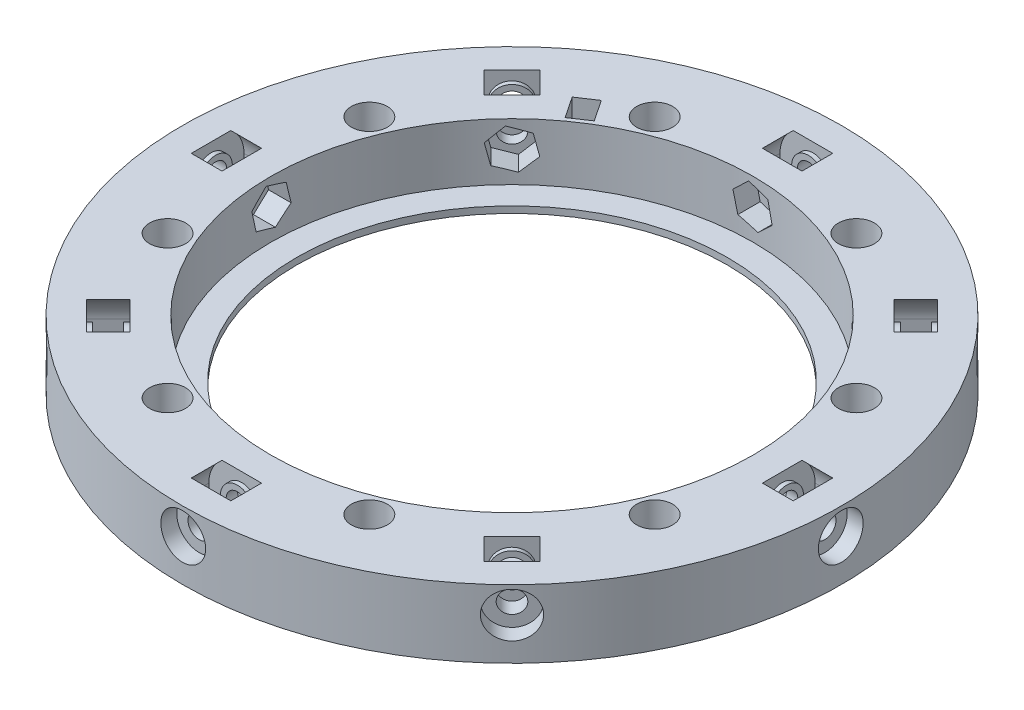
SolidWorks part; units mm, degrees
ref_plane "Front Plane" through (0, 0, 0) normal (0, 0, 1) x (1, 0, 0)
ref_plane "Top Plane" through (0, 0, 0) normal (0, 1, 0) x (1, 0, 0)
ref_plane "Right Plane" through (0, 0, 0) normal (1, 0, 0) x (0, 0, -1)
sketch "Sketch1" plane through (0, 0, 0) normal (0, 1, 0) x (1, 0, 0)
  circle A0 centre (0, 0) radius 75
  dimension "D1" = 150
extrude "Extrude-Thin1" add sketch "Sketch1" along normal blind 15.5 thin thin type one direction reverse wall 20.075
ref_plane "Plane1" through (0, 0, 75) normal (0, 0, 1) x (1, 0, 0)
sketch "Sketch2" plane through (0, 0, 75) normal (0, 0, 1) x (1, 0, 0)
  line L0 (-75, 0) -> (75, 0) construction
  line L1 (-7.5, 9.5) -> (-7.5, 0)
  line L2 (-7.5, 0) -> (7.5, 0)
  line L3 (7.5, 0) -> (7.5, 9.5)
  line L4 (75, 15.5) -> (-75, 15.5) construction
  arc A0 (7.5, 9.5) -> (-7.5, 9.5) centre (0, 9.5) ccw
  dimension "D1" = 15
  dimension "D2" = 6
extrude "Cut-Extrude1" cut sketch "Sketch2" against normal blind 7 from offset 6.5 offset against normal yes
sketch "Sketch3" plane through (0, 15.5, 0) normal (0, 1, 0) x (1, 0, 0)
  line L0 (0, 0) -> (0, 50000) construction
  line L1 (0, 0) -> (-19134.1716, 46193.9766) construction
  circle A0 centre (-22.961, 55.4328) radius 4.1
  dimension "D2" = 8.2
  dimension "D1" = 22.5
  dimension "D3" = 60
extrude "Cut-Extrude2" cut sketch "Sketch3" against normal blind 7.1
sketch "Sketch4" plane through (0, 15.5, 0) normal (0, 1, 0) x (1, 0, 0)
  circle A0 centre (-22.961, 55.4328) radius 2.05
  dimension "D1" = 4.1
extrude "Cut-Extrude3" cut sketch "Sketch4" against normal through all
pattern_circular "CirPattern2" count 8 over 360 about axis through (0, 15.5, 0) along (0, 1, 0) of "Cut-Extrude3", "Cut-Extrude2"
sketch "Sketch5" plane through (0, 0, 75) normal (0, 0, 1) x (1, 0, 0)
  circle A0 centre (0, 9.5) radius 2.55
  arc A1 (-4.5, 15.5) -> (-7.5, 9.5) centre (0, 9.5) ccw construction
  dimension "D1" = 5.1
extrude "Cut-Extrude4" cut sketch "Sketch5" against normal up to surface (20.1342 mm away) up to face at (54.925, 15.5, 0)
sketch "Sketch6" plane through (0, 0, 75) normal (0, 0, 1) x (1, 0, 0)
  circle A0 centre (0, 9.5) radius 5.1
  dimension "D1" = 10.2
extrude "Cut-Extrude5" cut sketch "Sketch6" against normal blind 3.8
sketch "Sketch7" plane through (0, 0, 75) normal (0, 0, 1) x (1, 0, 0)
  line L11 (-4.4735, 8.1369) -> (-1.0563, 4.9443)
  line L12 (-1.0563, 4.9443) -> (3.4172, 6.3074)
  line L13 (3.4172, 6.3074) -> (4.4735, 10.8631)
  line L14 (4.4735, 10.8631) -> (1.0563, 14.0557)
  line L15 (1.0563, 14.0557) -> (-3.4172, 12.6926)
  line L16 (-3.4172, 12.6926) -> (-4.4735, 8.1369)
  circle A0 centre (0, 9.5) radius 4.05 construction
  dimension "D1" = 8.1
extrude "Cut-Extrude6" cut sketch "Sketch7" against normal up to next from offset 15.1 offset against normal yes
sketch "Sketch8" plane through (0, 0, 75) normal (0, 0, 1) x (1, 0, 0)
  circle A0 centre (0, 9.5) radius 3.85
  circle A2 centre (0, 9.5) radius 2.55 construction
  circle A3 centre (0, 9.5) radius 2.55
  dimension "D1" = 7.7
extrude "Boss-Extrude1" add sketch "Sketch8" against normal blind 1 and the other way blind 1 from surface separate body starting at face at (2.55, 9.5, 68.5)
sketch "Sketch9" plane through (0, 0, 75) normal (0, 0, 1) x (1, 0, 0)
  circle A0 centre (0, 9.5) radius 2.55 construction
  circle A1 centre (0, 9.5) radius 2.55
  circle A3 centre (0, 9.5) radius 3.85
  circle A4 centre (0, 9.5) radius 3.85
  dimension "D2" = 0
extrude "Boss-Extrude2" add sketch "Sketch9" along normal blind 1 and the other way blind 1 from surface separate body starting at face at (2.55, 9.5, 61.5)
ref_axis "Axis1" through (0, 15.5, 0) along (0, -1, 0)
pattern_circular "CirPattern5" count 8 over 360 about axis through (0, 15.5, 0) along (0, -1, 0) of "Cut-Extrude5", "Cut-Extrude4", "Cut-Extrude1", "Cut-Extrude6"
pattern_circular "CirPattern13" count 8 over 360 about axis through (0, 15.5, 0) along (0, -1, 0) reverse direction yes of bodies 111 112
combine bodies "Combine1" bodies to combine 111 112 119 125 114 120 126 115 121 127 116 113 122 117 123 118 124
sketch "Sketch10" plane through (0, 15.5, 0) normal (0, 1, 0) x (1, 0, 0)
  line L0 (22.7646, 54.9585) -> (-18947.7116, -45743.8222) construction
  line L1 (7.7646, 58.9778) -> (-6462.7116, -49089.1679) construction
  circle A2 centre (7.8316, 59.4867) radius 4.15
  circle A3 centre (0, 0) radius 60 construction
  dimension "D1" = 15
  dimension "D2" = 8.3
extrude "Cut-Extrude7" [suppressed] cut sketch "Sketch10" against normal through all
pattern_circular "CirPattern14" [suppressed] count 8 over 360 of bodies 129
sketch "Sketch11" plane through (0, 15.5, 0) normal (0, 1, 0) x (1, 0, 0)
  line L0 (-33.0075, 45.0973) -> (-29.0331, 47.7529)
  line L5 (-29.0331, 47.7529) -> (-31.7165, 51.7689)
  line L6 (-31.7165, 51.7689) -> (-35.6909, 49.1133) construction
  line L7 (-35.6909, 49.1133) -> (-33.0075, 45.0973)
  line L8 (-47.8597, 34.0789) -> (41525.6209, 27812.5905) construction
  line L9 (0, 0) -> (-32.362, 48.4331) construction
  line L10 (0, -1000) -> (0, 49000) construction
  line L11 (-35.6909, 49.1133) -> (-29.0331, 47.7529) construction
  line L12 (-31.7165, 51.7689) -> (-33.0075, 45.0973) construction
  line L13 (-35.6909, 49.1133) -> (-36.2465, 49.9448)
  line L14 (-36.2465, 49.9448) -> (-32.272, 52.6004)
  line L15 (-32.272, 52.6004) -> (-31.7165, 51.7689)
  circle A1 centre (0, 0) radius 54.925 construction
  point P6 (-32.362, 48.4331)
  point P15 (-32.362, 48.4331)
  dimension "D1" = 33.75
  dimension "D2" = 4.78
  dimension "D3" = 4.83
  dimension "D4" = 58.25
  dimension "D5" = 1
extrude "Cut-Extrude8" cut sketch "Sketch11" against normal blind 3.66
sketch "Sketch12" plane through (0, 11.84, 0) normal (0, 1, 0) x (1, 0, 0)
  line L6 (-36.2465, 49.9448) -> (-32.272, 52.6004)
  line L7 (-32.272, 52.6004) -> (-31.7165, 51.7689)
  line L8 (-31.7165, 51.7689) -> (-35.6909, 49.1133)
  line L9 (-35.6909, 49.1133) -> (-36.2465, 49.9448)
  line L10 (-32.272, 52.6004) -> (-36.2465, 49.9448) construction
  line L11 (-29.0331, 47.7529) -> (-32.272, 52.6004) construction
  line L12 (-36.2465, 49.9448) -> (-33.0075, 45.0973) construction
  dimension "D1" = 1
extrude "Cut-Extrude9" cut sketch "Sketch12" against normal up to next
sketch "Sketch13" plane through (0, 0, 0) normal (0, -1, 0) x (1, 0, 0)
  circle A0 centre (0, 0) radius 54.925
  circle A1 centre (0, 0) radius 49
  dimension "D1" = 98
extrude "Boss-Extrude3" add sketch "Sketch13" against normal blind 1.5 from offset 1 offset against normal yes
